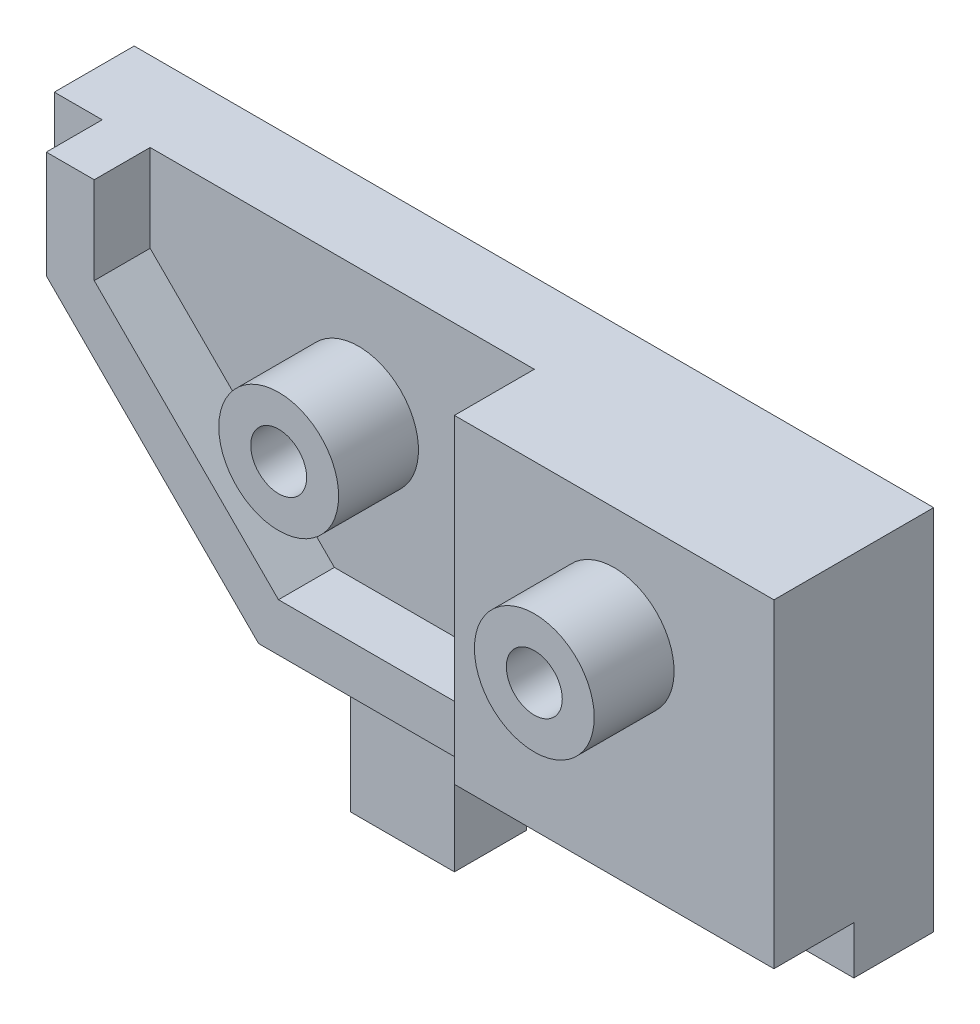
SolidWorks part; units mm, degrees
ref_plane "Front Plane" through (0, 0, 0) normal (0, 0, 1) x (1, 0, 0)
ref_plane "Top Plane" through (0, 0, 0) normal (0, 1, 0) x (1, 0, 0)
ref_plane "Right Plane" through (0, 0, 0) normal (1, 0, 0) x (0, 0, -1)
sketch "Sketch1" plane through (0, 0, 0) normal (0, 1, 0) x (1, 0, 0)
  line L0 (18, 0) -> (22, 0)
  line L1 (0, 0) -> (18, 0)
  line L2 (0, 0) -> (0, -5)
  line L3 (0, -5) -> (15, -5)
  line L4 (18, 0) -> (18, -10) construction
  line L6 (15, -5) -> (15, -10)
  line L7 (15, -10) -> (35, -10)
  line L8 (35, -5) -> (35, -10)
  line L10 (35, -5) -> (35, 0)
  line L11 (35, 0) -> (22, 0)
  dimension "D1" = 5
  dimension "D2" = 18
  dimension "D3" = 5
  dimension "D4" = 20
  dimension "D5" = 15
extrude "Boss-Extrude1" add sketch "Sketch1" along normal blind 23
sketch "Sketch2" plane through (0, 0, 10) normal (0, 0, 1) x (1, 0, 0)
  line L0 (35, 16) -> (25, 16) construction
  line L1 (35, 23) -> (35, 0) construction
  line L2 (15, 0) -> (35, 0) construction
  line L3 (0, 23) -> (0, 0) construction
  line L4 (0, 0) -> (15, 0) construction
  circle A0 centre (4, 15) radius 1.75
  circle A1 centre (25, 16) radius 1.75
  dimension "D5" = 3.5
  dimension "D6" = 3.5
  dimension "D1" = 10
  dimension "D2" = 16
  dimension "D3" = 4
  dimension "D4" = 15
extrude "Cut-Extrude1" cut sketch "Sketch2" against normal blind 10
sketch "Sketch3" plane through (0, 0, 0) normal (0, -1, 0) x (1, 0, 0)
  line L0 (0, 2.5) -> (35, 2.5) construction
  line L1 (25, 0) -> (25, 10) construction
  line L2 (35, 0) -> (0, 0) construction
  line L3 (15, 10) -> (35, 10) construction
  line L4 (0, 0) -> (0, 5) construction
  line L5 (35, 10) -> (35, 0) construction
  circle A1 centre (25, 2.5) radius 1.75
  point P1 (25, 10)
  dimension "D1" = 3.5
sketch "Sketch4" plane through (0, 0, 0) normal (0, -1, 0) x (1, 0, 0)
  line L0 (0, 2.5) -> (35, 2.5) construction
  line L1 (0, 0) -> (0, 5) construction
  line L2 (0, 5) -> (15, 5) construction
  line L3 (35, 10) -> (35, 0) construction
  line L7 (9.75, 0.25) -> (3.25, 0.25)
  line L8 (9.75, 0.25) -> (9.75, 4.75)
  line L9 (9.75, 4.75) -> (3.25, 4.75)
  line L10 (3.25, 0.25) -> (3.25, 4.75)
  line L11 (9.75, 0.25) -> (3.25, 4.75) construction
  line L12 (9.75, 4.75) -> (3.25, 0.25) construction
  point P12 (6.5, 2.5)
  dimension "D1" = 0.25
  dimension "D2" = 6.5
  dimension "D3" = 3.25
extrude "Boss-Extrude2" add sketch "Sketch4" along normal blind 7
sketch "Sketch6" plane through (0, 0, 5) normal (0, 0, 1) x (1, 0, 0)
  circle A0 centre (4, 15) radius 1.75
  circle A1 centre (4, 15) radius 3.75
  dimension "D1" = 2
  dimension "D2" = 3.5
extrude "Boss-Extrude3" add sketch "Sketch6" along normal blind 5
sketch "Sketch7" plane through (0, 0, 10) normal (0, 0, 1) x (1, 0, 0)
  circle A0 centre (25, 16) radius 1.75
  circle A1 centre (25, 16) radius 3.75
  dimension "D1" = 3.5
  dimension "D2" = 2
extrude "Boss-Extrude4" add sketch "Sketch7" along normal blind 5 contours A1 | A0
sketch "Sketch10" plane through (0, 0, 5) normal (0, 0, 1) x (1, 0, 0)
  line L0 (0, 23) -> (-15.0472, 23)
  line L1 (-15.0472, 15.0472) -> (0, 0)
  line L2 (0, 23) -> (0, 0) construction
  line L3 (-15.0472, 23) -> (-15.0472, 15.0472)
  line L4 (0, 23) -> (0, 0)
  dimension "D1" = 45
  dimension "D2" = 21.28
extrude "Boss-Extrude5" add sketch "Sketch10" against normal blind 5
sketch "Sketch11" plane through (0, 0, 5) normal (0, 0, 1) x (1, 0, 0)
  line L0 (-12.0472, 23) -> (-12.0472, 16.2899)
  line L1 (-15.0472, 23) -> (15, 23) construction
  line L2 (-12.0472, 16.2899) -> (1.2426, 3)
  line L3 (1.2426, 3) -> (15, 3)
  line L4 (15, 23) -> (15, 0) construction
  line L5 (-15.0472, 23) -> (-15.0472, 15.0472) construction
  line L6 (-15.0472, 15.0472) -> (0, 0) construction
  line L7 (0, 0) -> (15, 0) construction
  line L8 (-9.0472, 23) -> (-9.0472, 17.5325)
  line L9 (-9.0472, 17.5325) -> (2.4853, 6)
  line L10 (2.4853, 6) -> (15, 6)
  line L11 (-12.0472, 23) -> (-9.0472, 23)
  line L12 (15, 6) -> (15, 3)
  dimension "D1" = 3
  dimension "D2" = 3
  dimension "D3" = 3
  dimension "D4" = 3
extrude "Boss-Extrude6" add sketch "Sketch11" along normal blind 3.5
extrude "Cut-Extrude2" cut sketch "Sketch3" against normal blind 10 contours A1
sketch "Sketch12" plane through (15, 0, 0) normal (-1, 0, 0) x (0, 0, 1)
  line L1 (5, 3) -> (10, 3)
  line L2 (5, 3) -> (5, 0)
  line L3 (5, 0) -> (10, 0)
  line L4 (10, 3) -> (10, 0)
extrude "Cut-Extrude3" cut sketch "Sketch12" against normal up to surface (20 mm away) up to face at (35, 11.5, 5)
sketch "Sketch13" plane through (0, 0, 0) normal (0, 0, -1) x (-1, 0, 0)
  circle A0 centre (-25, 16) radius 2.5
  circle A1 centre (-4, 15) radius 2.5
  dimension "D1" = 5
  dimension "D2" = 5
extrude "Cut-Extrude4" cut sketch "Sketch13" against normal blind 4
